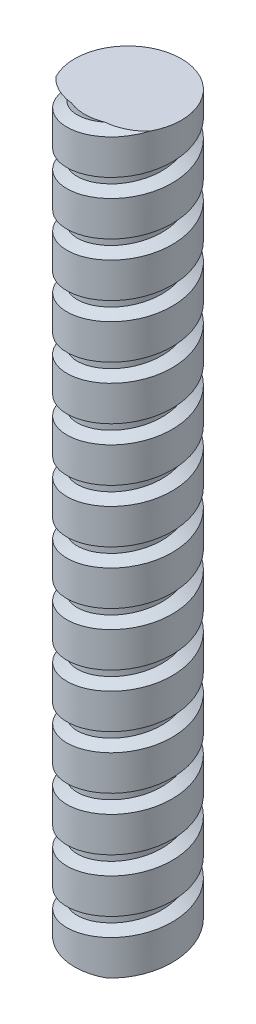
SolidWorks part; units mm, degrees
ref_plane "Plano frontal" through (0, 0, 0) normal (0, 0, 1) x (1, 0, 0)
ref_plane "Plano superior" through (0, 0, 0) normal (0, 1, 0) x (1, 0, 0)
ref_plane "Plano direito" through (0, 0, 0) normal (1, 0, 0) x (0, 0, -1)
sketch "Esboço1" plane through (0, 0, 0) normal (0, 1, 0) x (1, 0, 0)
  circle A0 centre (0, 0) radius 4
  dimension "D1" = 8
extrude "Ressalto-extrusão1" add sketch "Esboço1" along normal mid plane 55
sketch "Esboço2" plane through (0, -27.5, 0) normal (0, -1, 0) x (-1, 0, 0)
  circle A0 centre (0, 0) radius 4
  dimension "D1" = 8
curve "Hélice/Espiral1" pitch 4 height 105.5 radius 4 centre (0, -27.5, 0) axis (0, 1, 0) start towards (1, 0, 0)
sketch "Esboço3" plane through (0, 0, 0) normal (1, 0, 0) x (0, 0, -1)
  line L0 (4, -25.815) -> (4, -27.185)
  line L1 (4, -27.185) -> (3.24, -26.755)
  line L2 (3.24, -26.755) -> (3.24, -26.245)
  line L3 (3.24, -26.245) -> (4, -25.815)
  point P3 (4, -26.5)
  dimension "D1" = 0.51
  dimension "D3" = 59
sweep "Varredura de corte1" cut profiles "Esboço3" path "Hélice/Espiral1" align with end faces yes
sketch "Esboço4" plane through (0, -27.5, 0) normal (0, -1, 0) x (-1, 0, 0)
  circle A0 centre (0, 0) radius 2.55
  dimension "D1" = 5.1
extrude "Corte-extrusão1" cut sketch "Esboço4" against normal blind 20
